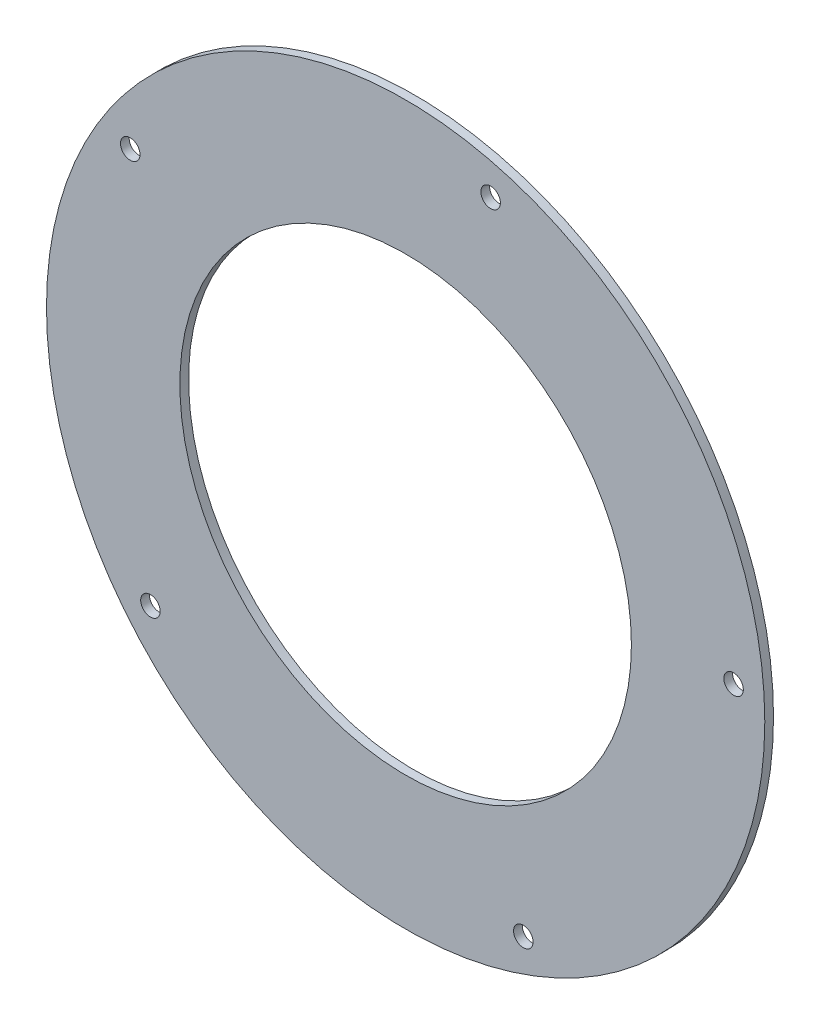
SolidWorks part; units mm, degrees
ref_plane "Front Plane" through (0, 0, 0) normal (0, 0, 1) x (1, 0, 0)
ref_plane "Top Plane" through (0, 0, 0) normal (0, 1, 0) x (1, 0, 0)
ref_plane "Right Plane" through (0, 0, 0) normal (1, 0, 0) x (0, 0, -1)
ref_axis "X-Axis" through (-88.99, 0, 0) along (1, 0, 0)
ref_axis "Y-Axis" through (0, 55, 0) along (0, -1, 0)
ref_axis "Z-Axis" through (0, 0, -88.99) along (0, 0, 1)
sketch "Sketch1" plane through (0, 0, 0) normal (0, 0, 1) x (1, 0, 0)
  circle A0 centre (0, 0) radius 35
  dimension "D1" = 70
extrude "Boss-Extrude1" add sketch "Sketch1" along normal blind 1.3
sketch "Sketch2" plane through (0, 0, 1.3) normal (0, 0, 1) x (1, 0, 0)
  circle A0 centre (0, 0) radius 22
  dimension "D1" = 44
extrude "Cut-Extrude1" cut sketch "Sketch2" against normal through all
sketch "Sketch3" plane through (0, 0, 1.3) normal (0, 0, 1) x (1, 0, 0)
  line L0 (0, 0) -> (0, 27) construction
  circle A0 centre (0, 27) radius 1
  dimension "D1" = 2
  dimension "D2" = 27
extrude "Cut-Extrude2" [suppressed] cut sketch "Sketch3" against normal through all
sketch "Sketch4" [suppressed] plane through (0, 0, 1.3) normal (0, 0, 1) x (1, 0, 0)
  circle A0 centre (0, 27) radius 3.1
  dimension "D1" = 6.2
extrude "Cut-Extrude3" [suppressed] cut sketch "Sketch4" against normal through all from offset 0.3 offset against normal yes
pattern_circular "CirPattern1" [suppressed] count 16 over 360 about axis through (0, 0, -88.99) along (0, 0, 1) of bodies 105
other "Move Face1" flip direction yes face at (22, 0, 0) offset 0.7 parameters "D1"=0.7
sketch "Sketch5" plane through (0, 0, 1.3) normal (0, 0, 1) x (1, 0, 0)
  line L0 (0, 0) -> (0, 35) construction
  line L1 (0, 0) -> (8.2822, 30.9096) construction
  circle A0 centre (0, 0) radius 35 construction
  circle A1 centre (8.2822, 30.9096) radius 0.95
  dimension "D3" = 1.9
  dimension "D1" = 15
  dimension "D2" = 32
extrude "Cut-Extrude4" cut sketch "Sketch5" against normal through all
pattern_circular "CirPattern2" count 5 over 360 about axis through (0, 0, -88.99) along (0, 0, 1) of "Cut-Extrude4"
other "Move Face2" face at (-26.5439, 18.332, 1.3) offset 0.25 parameters "D1"=0.25
